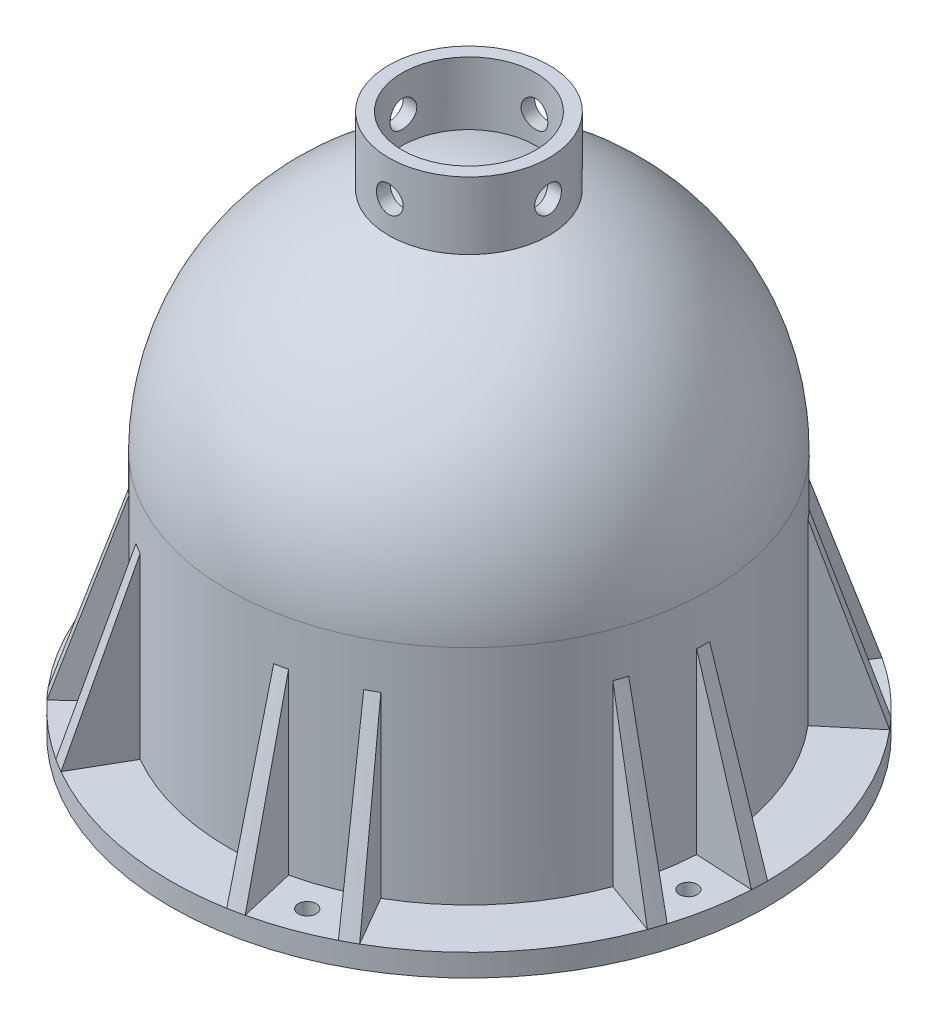
SolidWorks part; units mm, degrees
material "Polyester Resin"
ref_plane "Front Plane" through (0, 0, 0) normal (0, 0, 1) x (1, 0, 0)
ref_plane "Top Plane" through (0, 0, 0) normal (0, 1, 0) x (1, 0, 0)
ref_plane "Right Plane" through (0, 0, 0) normal (1, 0, 0) x (0, 0, -1)
ref_axis "Axis1" through (0, 98.5378, 0) along (0, -1, 0)
sketch "Sketch1" plane through (0, 0, 0) normal (0, 0, 1) x (1, 0, 0)
  line L0 (0, 0) -> (50, 0) construction
  line L1 (54, 0) -> (54, -50)
  line L2 (50, -50) -> (54, -50) construction
  line L3 (0, 98.5378) -> (0, -108.4725) construction
  line L4 (50, 0) -> (54, 0) construction
  line L6 (0, 54) -> (0, 50)
  line L7 (50, 0) -> (50, -50)
  line L8 (50, -50) -> (50, -55) construction
  line L9 (50, -55) -> (50, -64)
  line L10 (46, -55) -> (46, -50)
  line L11 (54, -50) -> (67, -50)
  line L12 (67, -50) -> (67, -55)
  line L13 (50, -64) -> (46, -64)
  line L14 (46, -64) -> (46, -55)
  line L15 (50, -55) -> (67, -55)
  line L16 (46, -50) -> (50, -50)
  line L17 (50, -55) -> (46, -55) construction
  arc A0 (54, 0) -> (0, 54) centre (0, 0) ccw
  arc A1 (50, 0) -> (0, 50) centre (0, 0) ccw
  dimension "D1" = 50
  dimension "D2" = 9
  dimension "D3" = 5
  dimension "D4" = 4
  dimension "D5" = 4
  dimension "D6" = 50
  dimension "D7" = 13
revolve "Revolve1" add sketch "Sketch1" angle 360 about axis through (0, 98.5378, 0) along (0, -1, 0)
fillet "Fillet1" radius 2 2 edges at (0, -50, 50) (0, -50, 46)
fillet "Fillet3" radius 1.5 2 edges at (0, -64, 46) (0, -64, 50)
sketch "Sketch2" plane through (0, 0, 0) normal (0, 0, 1) x (1, 0, 0)
  line L0 (54, -10) -> (67, -50)
  line L1 (67, -50) -> (54, -50)
  line L2 (54, -50) -> (54, -10)
  line L3 (54, -50) -> (54, 0) construction
  dimension "D1" = 40
revolve "Revolve2" add sketch "Sketch2" angle 3 about axis through (0, 98.5378, 0) along (0, -1, 0)
pattern_circular "CirPattern1" count 2 every 17 about axis through (0, 98.5378, 0) along (0, -1, 0) of "Revolve2"
sketch "Sketch3" plane through (0, -50, 0) normal (0, 1, 0) x (1, 0, 0)
  line L0 (51.6405, -15.7881) -> (53.926, -2.8261) construction
  line L1 (53.926, -2.8261) -> (61.0775, -3.2009) construction
  line L2 (53.926, -2.8261) -> (66.9082, -3.5065) construction
  line L3 (61.0775, -3.2009) -> (58.4889, -17.8819) construction
  line L4 (51.6405, -15.7881) -> (64.0724, -19.5889) construction
  line L5 (58.4889, -17.8819) -> (51.6405, -15.7881) construction
  line L6 (52.7832, -9.3071) -> (59.7832, -10.5414) construction
  circle A0 centre (59.7832, -10.5414) radius 2
  circle A1 centre (59.7832, -10.5414) radius 6 construction
  dimension "D2" = 4
  dimension "D3" = 12
  dimension "D1" = 7
extrude "Cut-Extrude1" cut sketch "Sketch3" against normal up to next contours A0
pattern_circular "CirPattern2" count 6 over 360 about axis through (0, 98.5378, 0) along (0, -1, 0) of "Cut-Extrude1", "Revolve2", "CirPattern1"
ref_plane "Plane2" through (0, 40, 0) normal (0, 1, 0) x (1, 0, 0)
sketch "Sketch4" plane through (0, 0, 0) normal (0, 1, 0) x (1, 0, 0)
  line L0 (0, 0) -> (0, -15) construction
  line L1 (0, -15) -> (0, -17.5) construction
  line L2 (0, -17.5) -> (0, -18.5) construction
  line L3 (0, -18.5) -> (0, -21) construction
  circle A0 centre (0, 0) radius 15 construction
  circle A1 centre (0, 0) radius 17.5 construction
  circle A2 centre (0, 0) radius 18.5
  circle A3 centre (0, 0) radius 21
  dimension "D1" = 15
  dimension "D2" = 2.5
  dimension "D3" = 1
  dimension "D4" = 2.5
extrude "Boss-Extrude1" add sketch "Sketch4" along normal up to surface (46.4516 mm away) from offset 0 up to face at (0, 0, 50)
sketch "Sketch6" plane through (0, 0, 0) normal (0, 1, 0) x (1, 0, 0)
  line L0 (0, -45.5) -> (0, -50) construction
  line L1 (-26.4307, -42.4431) -> (-26.4307, -31.6388)
  line L2 (-29.4307, -40.4207) -> (-29.4307, -31.6388)
  line L3 (-29.4307, -40.4207) -> (-26.4307, -40.4207) construction
  line L4 (-40.4207, -29.4307) -> (-31.6388, -29.4307)
  line L5 (-42.4431, -26.4307) -> (-31.6388, -26.4307)
  line L6 (-40.4207, -29.4307) -> (-40.4207, -26.4307) construction
  line L7 (0, 0) -> (-27.9307, -27.9307) construction
  arc A0 (-26.4307, -31.6388) -> (-31.6388, -26.4307) centre (-27.9307, -27.9307) ccw
  circle A1 centre (0, 0) radius 45.5 construction
  circle A2 centre (0, 0) radius 50 construction
  circle A3 centre (-27.9307, -27.9307) radius 1.25
  arc A4 (-31.6388, -29.4307) -> (-29.4307, -31.6388) centre (-27.9307, -27.9307) ccw
  arc A5 (-42.4431, -26.4307) -> (-40.4207, -29.4307) centre (0, 0) ccw
  arc A6 (-29.4307, -40.4207) -> (-26.4307, -42.4431) centre (0, 0) ccw
  point P19 (-27.9307, -40.4207)
  point P21 (-40.4207, -27.9307)
  dimension "D3" = 8
  dimension "D5" = 2.5
  dimension "D1" = 4.5
  dimension "D2" = 3
  dimension "D4" = 6
extrude "Boss-Extrude2" add sketch "Sketch6" along normal up to surface (25.1559 mm away) contours L2 A6 L1 A0 L5 A5 L4 A4 A3 region at (-30.3615, 0, 30.3615) up to face at (0, 0, 50)
pattern_circular "CirPattern3" count 2 over 360 about axis through (0, 98.5378, 0) along (0, -1, 0) of "Boss-Extrude2"
ref_plane "Plane3" through (0, 66, 0) normal (0, 1, 0) x (1, 0, 0)
sketch "Sketch7" plane through (0, 66, 0) normal (0, 1, 0) x (1, 0, 0)
  line L0 (0, 18) -> (0, 15) construction
  line L1 (0, 15) -> (0, 0) construction
  circle A0 centre (0, 0) radius 15
  circle A1 centre (0, 0) radius 18
  dimension "D2" = 30
  dimension "D1" = 3
extrude "Boss-Extrude3" add sketch "Sketch7" against normal up to surface (14.1252 mm away) up to face at (0, 0, 54)
sketch "Sketch8" plane through (0, 0, 0) normal (0, 0, 1) x (1, 0, 0)
  line L0 (0, 66) -> (0, 50.9117) construction
  line L1 (15, 66) -> (-15, 66) construction
  line L2 (-18, 50.9117) -> (18, 50.9117) construction
  circle A0 centre (0, 58) radius 3
  point P8 (0, 61)
  dimension "D1" = 6
  dimension "D2" = 5
extrude "Cut-Extrude2" cut sketch "Sketch8" against normal through all and the other way through all
pattern_circular "CirPattern4" count 2 every 90 about axis through (0, 98.5378, 0) along (0, -1, 0) of "Cut-Extrude2"
